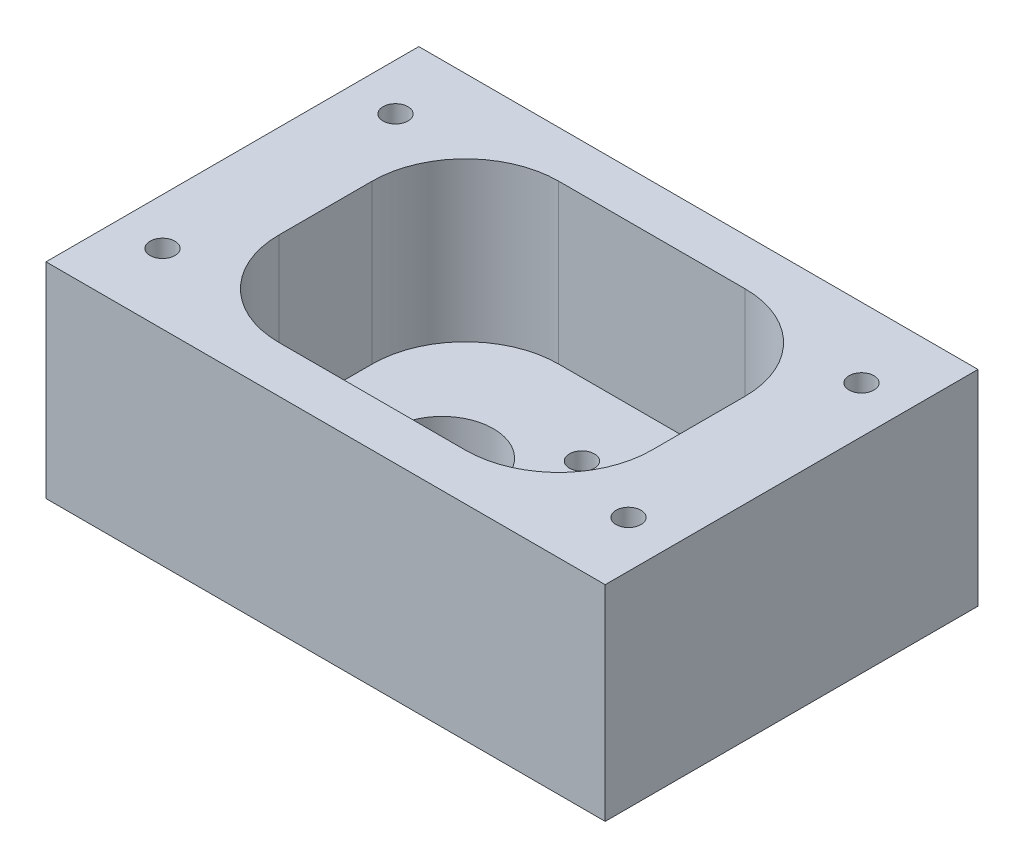
SolidWorks part; units mm, degrees
material "6061 Alloy"
ref_plane "Front Plane" through (0, 0, 0) normal (0, 0, 1) x (1, 0, 0)
ref_plane "Top Plane" through (0, 0, 0) normal (0, 1, 0) x (1, 0, 0)
ref_plane "Right Plane" through (0, 0, 0) normal (1, 0, 0) x (0, 0, -1)
sketch "Sketch1" plane through (0, 0, 0) normal (0, 1, 0) x (1, 0, 0)
  line L1 (-38.1, -25.4) -> (38.1, -25.4)
  line L2 (-38.1, -25.4) -> (-38.1, 25.4)
  line L3 (-38.1, 25.4) -> (38.1, 25.4)
  line L4 (38.1, -25.4) -> (38.1, 25.4)
  line L5 (-38.1, -25.4) -> (38.1, 25.4) construction
  line L6 (-38.1, 25.4) -> (38.1, -25.4) construction
  point P0 (0, 0)
  dimension "D1" = 76.2
  dimension "D2" = 50.8
extrude "Boss-Extrude1" add sketch "Sketch1" along normal blind 27.94
sketch "Sketch2" plane through (0, 0, 0) normal (0, -1, 0) x (1, 0, 0)
  line L0 (-38.1, 0) -> (38.1, 0) construction
  line L1 (-38.1, -25.4) -> (-38.1, 25.4) construction
  line L2 (38.1, 25.4) -> (38.1, -25.4) construction
  line L3 (0, 25.4) -> (0, -25.4) construction
  line L4 (-38.1, 25.4) -> (38.1, 25.4) construction
  line L5 (38.1, -25.4) -> (-38.1, -25.4) construction
  circle A0 centre (-9.525, 0) radius 6.985
  circle A1 centre (9.525, 0) radius 9
  point P12 (-9.525, 0)
  point P13 (9.525, 0)
  dimension "D3" = 18
  dimension "D4" = 13.97
  dimension "D1" = 19.05
  dimension "D2" = 9.525
extrude "Cut-Extrude1" cut sketch "Sketch2" against normal through all contours A0 | A1
sketch "Sketch3" plane through (0, 27.94, 0) normal (0, 1, 0) x (1, 0, 0)
  line L0 (9.525, 0) -> (-9.525, 0) construction
  line L1 (-12.7, -19.05) -> (12.7, -19.05)
  line L2 (-25.4, -6.35) -> (-25.4, 6.35)
  line L3 (-12.7, 19.05) -> (12.7, 19.05)
  line L4 (25.4, -6.35) -> (25.4, 6.35)
  line L5 (-25.4, -19.05) -> (25.4, 19.05) construction
  line L6 (-25.4, 19.05) -> (25.4, -19.05) construction
  arc A0 (12.7, 19.05) -> (25.4, 6.35) centre (12.7, 6.35) cw
  arc A1 (25.4, -6.35) -> (12.7, -19.05) centre (12.7, -6.35) cw
  arc A2 (-12.7, -19.05) -> (-25.4, -6.35) centre (-12.7, -6.35) cw
  arc A3 (-25.4, 6.35) -> (-12.7, 19.05) centre (-12.7, 6.35) cw
  point P0 (0, 0)
  dimension "D3" = 12.7
  dimension "D1" = 38.1
  dimension "D2" = 50.8
extrude "Cut-Extrude2" cut sketch "Sketch3" against normal blind 21.59
sketch "Sketch4" plane through (0, 0, 0) normal (0, -1, 0) x (1, 0, 0)
  line L0 (-31.75, 25.4) -> (-31.75, -25.4) construction
  line L1 (-38.1, 25.4) -> (38.1, 25.4) construction
  line L2 (38.1, -25.4) -> (-38.1, -25.4) construction
  line L3 (31.75, 25.4) -> (31.75, -25.4) construction
  line L4 (-38.1, -25.4) -> (-38.1, 25.4) construction
  line L5 (38.1, 25.4) -> (38.1, -25.4) construction
  line L6 (-31.75, 0) -> (31.75, 0) construction
  line L7 (0.3326, 9.1924) -> (18.7174, -9.1924) construction
  line L8 (18.7174, 9.1924) -> (0.3326, -9.1924) construction
  circle A1 centre (9.525, 0) radius 9 construction
  point P12 (-31.75, 15.875)
  point P13 (-31.75, -15.875)
  point P14 (31.75, 15.875)
  point P15 (31.75, -15.875)
  point P20 (9.525, 0)
  point P25 (9.525, 0)
  point P27 (0.3326, 9.1924)
  point P28 (18.7174, 9.1924)
  point P29 (18.7174, -9.1924)
  point P30 (0.3326, -9.1924)
  dimension "D1" = 6.35
  dimension "D2" = 6.35
  dimension "D3" = 31.75
  dimension "D4" = 45
  dimension "D5" = 45
  dimension "D6" = 26
hole_wizard "M3 Clearance Hole1" positions "3DSketch1" profile "Sketch5" hole size "M3" standard "ANSI Metric" end condition through all
sketch3d "3DSketch1"
  point P0 (-31.75, 0, 15.875)
  point P3 (-31.75, 0, -15.875)
  point P6 (0.3326, 0, 9.1924)
  point P9 (0.3326, 0, -9.1924)
  point P12 (18.7174, 0, 9.1924)
  point P15 (18.7174, 0, -9.1924)
  point P18 (31.75, 0, 15.875)
  point P21 (31.75, 0, -15.875)
sketch "Sketch5" plane through (-31.75, 0, 15.875) normal (1, 0, 0) x (0, 0, -1)
  line L0 (0, 0) -> (0, 27.94)
  line L1 (0, 27.94) -> (1.7, 27.94)
  line L2 (1.7, 27.94) -> (1.7, 0)
  line L5 (1.7, 0) -> (0, 0)
  line L11 (0, -6.35) -> (0, 107.95) construction
  dimension "Thru Hole Dia." = 3.4
  dimension "Thru Hole Depth" = 27.94
equation "\"D2@Sketch4\"=\"D1@Sketch4\""
equation "\"D2@Sketch2\"=\"D1@Sketch2\"/2"
